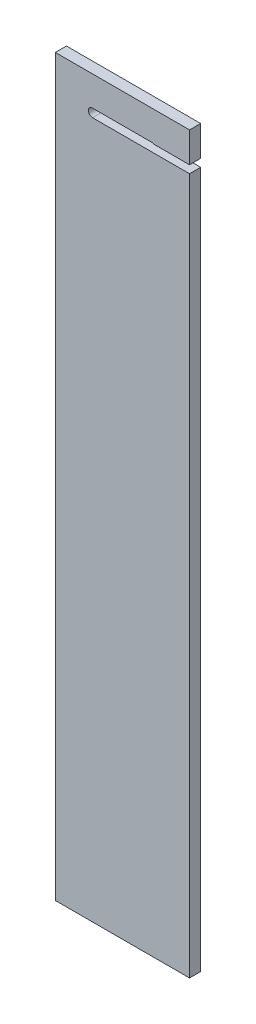
SolidWorks part; units mm, degrees
ref_plane "Front Plane" through (0, 0, 0) normal (0, 0, 1) x (1, 0, 0)
ref_plane "Top Plane" through (0, 0, 0) normal (0, 1, 0) x (1, 0, 0)
ref_plane "Right Plane" through (0, 0, 0) normal (1, 0, 0) x (0, 0, -1)
sketch "Sketch1" plane through (0, 0, 0) normal (0, 0, 1) x (1, 0, 0)
  line L0 (0, 149.225) -> (0, -149.225) construction
  line L1 (-28.75, 149.225) -> (28.75, 149.225)
  line L2 (-28.75, 149.225) -> (-28.75, -149.225)
  line L3 (-28.75, -149.225) -> (28.75, -149.225)
  line L4 (28.75, 149.225) -> (28.75, -149.225)
  line L5 (28.75, 152.527) -> (12.827, 152.527)
  line L10 (0, 149.225) -> (0, 165.481) construction
  line L11 (12.827, 152.527) -> (12.827, 152.781)
  line L12 (-28.75, 149.225) -> (28.75, 149.225)
  line L13 (-28.75, 149.225) -> (-28.75, 165.481)
  line L14 (-28.75, 165.481) -> (28.75, 165.481)
  line L15 (28.75, 149.225) -> (28.75, 165.481)
  line L16 (12.827, 152.781) -> (-12.827, 152.781)
  line L17 (-12.827, 152.781) -> (-12.827, 149.225)
  arc A0 (-12.827, 152.781) -> (-12.827, 149.225) centre (-12.827, 151.003) ccw
  point P6 (0, 0)
  point P21 (0, 152.781)
  dimension "D3" = 12.7
  dimension "D1" = 298.45
  dimension "D2" = 57.5
  dimension "D4" = 0.254
  dimension "D5" = 3.302
  dimension "D6" = 25.654
extrude "Boss-Extrude1" add sketch "Sketch1" along normal blind 4.7625 contours L4 L12 L1 L2 L3 | L17 L16 L11 L5 L15 L14 L13 L1 region at (-1.3049, 158.5635, 0) region at (0, 0, 0)
fillet "Fillet1" radius 3.175 1 edges at (12.827, 152.527, 2.3813)
equation "\"Height\"= 12in"
equation "\"Depth\"= 7in"
equation "\"WallThickness\"= 0.1875in"
equation "\"FloorThickness\"= 0.1875in"
equation "\"Width\" = 30in"
equation "\"D1@Boss-Extrude1\"=\"WallThickness\""
